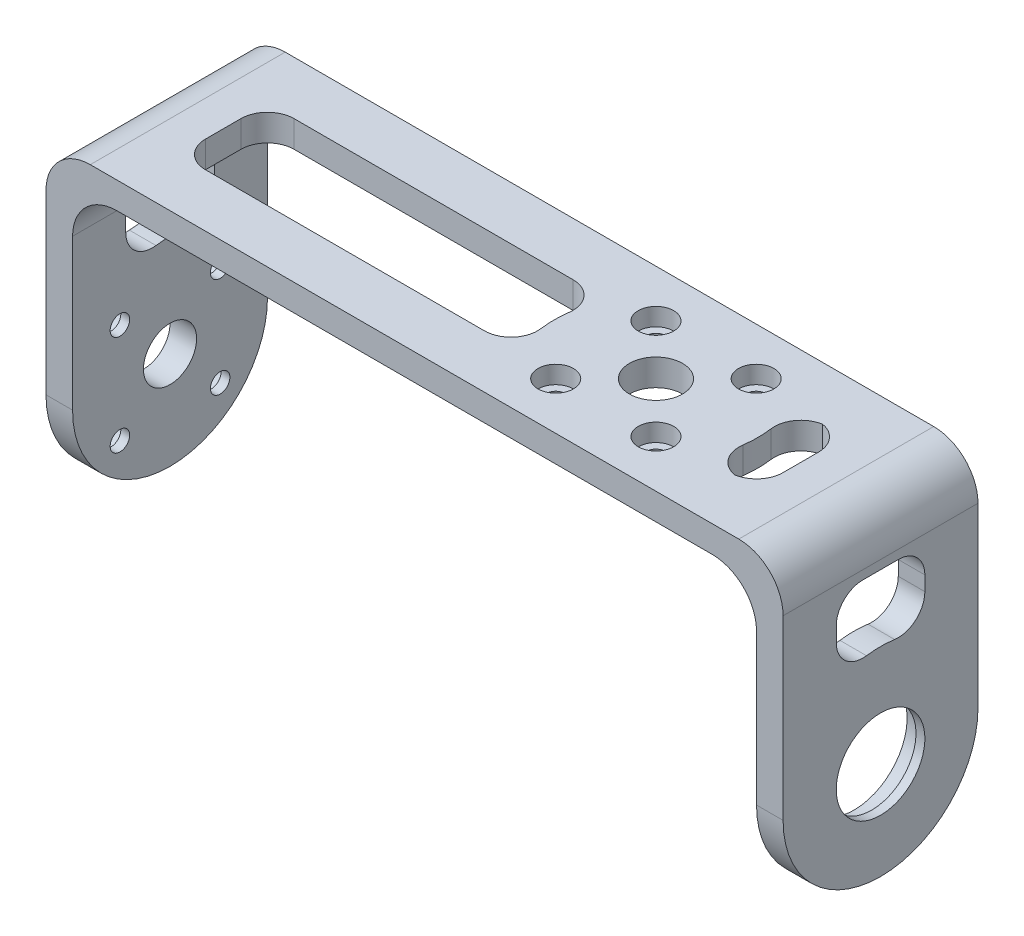
SolidWorks part; units mm, degrees
ref_plane "Front Plane" through (0, 0, 0) normal (0, 0, 1) x (1, 0, 0)
ref_plane "Top Plane" through (0, 0, 0) normal (0, 1, 0) x (1, 0, 0)
ref_plane "Right Plane" through (0, 0, 0) normal (1, 0, 0) x (0, 0, -1)
sketch "Sketch1" plane through (0, 0, 0) normal (0, 1, 0) x (1, 0, 0)
  line L0 (16.25, 0) -> (18.3713, 2.1213) construction
  line L1 (38.6, 11) -> (-38.6, 11)
  line L2 (38.6, 11) -> (38.6, -11)
  line L3 (38.6, -11) -> (-38.6, -11)
  line L4 (-38.6, 11) -> (-38.6, -11)
  line L5 (38.6, 11) -> (-38.6, -11) construction
  line L6 (38.6, -11) -> (-38.6, 11) construction
  line L7 (-38.6, 11) -> (-41.6, 11)
  line L8 (-38.6, 11) -> (-38.6, -11)
  line L9 (-38.6, -11) -> (-41.6, -11)
  line L10 (-41.6, 11) -> (-41.6, -11)
  line L11 (38.6, 11) -> (41.6, 11)
  line L12 (38.6, 11) -> (38.6, -11)
  line L13 (38.6, -11) -> (41.6, -11)
  line L14 (41.6, 11) -> (41.6, -11)
  line L15 (-32.6, 5) -> (-32.6, 11) construction
  line L16 (32.6, 5) -> (26.6062, 5)
  line L17 (32.6, 5) -> (32.6, -5)
  line L18 (32.6, -5) -> (26.6062, -5)
  line L19 (-32.6, 5) -> (-32.6, -5)
  line L20 (32.6, 5) -> (-32.6, -5) construction
  line L21 (32.6, -5) -> (-32.6, 5) construction
  line L22 (-32.6, 5) -> (-38.6, 5) construction
  line L23 (5.8938, 5) -> (-32.6, 5)
  line L24 (5.8938, -5) -> (-32.6, -5)
  circle A0 centre (16.25, 0) radius 3
  arc A1 (5.8938, 5) -> (5.8938, -5) centre (16.25, 0) ccw
  arc A2 (26.6062, -5) -> (26.6062, 5) centre (16.25, 0) ccw
  point P0 (0, 0)
  point P13 (0, 0)
  dimension "D5" = 6
  dimension "D8" = 23
  dimension "D1" = 77.2
  dimension "D2" = 22
  dimension "D3" = 3
  dimension "D4" = 22.35
  dimension "D6" = 45
  dimension "D7" = 6
extrude "Boss-Extrude1" add sketch "Sketch1" against normal blind 3 contours L1 L4 L3 L2 region at (37.7973, 0, 0)
extrude "Boss-Extrude2" add sketch "Sketch1<3>" against normal blind 36 separate body contours L7 L10 L9 L4 | L14 L11 L2 L13 region at (40.1, 0, 0) region at (-40.1, 0, 0)
sketch "Sketch1<3>" plane through (0, 0, 0) normal (0, 1, 0) x (1, 0, 0) same geometry as "Sketch1"
sketch "Sketch2" plane through (-41.6, 0, 0) normal (-1, 0, 0) x (0, 0, 1)
  line L0 (0, -25) -> (5.6569, -19.3431) construction
  line L3 (-11, -36) -> (11, -36) construction
  circle A0 centre (0, -25) radius 3
  circle A1 centre (5.6569, -19.3431) radius 1.1
  dimension "D1" = 6
  dimension "D5" = 2.2
  dimension "D2" = 11
  dimension "D3" = 8
  dimension "D4" = 45
extrude "Cut-Extrude1" cut sketch "Sketch2" against normal up to surface (3 mm away) contours A0 | A1 region at (-41.6, -25, 0) up to face at (-38.6, -18, 0)
sketch "Sketch4" plane through (0, 0, 0) normal (0, 1, 0) x (1, 0, 0)
  line L0 (21.9069, 5.6569) -> (16.25, 0) construction
  line L1 (38.6, 11) -> (-38.6, 11) construction
  circle A0 centre (21.9069, 5.6569) radius 1.1
  dimension "D3" = 2.2
  dimension "D1" = 45
  dimension "D2" = 8
extrude "Cut-Extrude3" cut sketch "Sketch4" against normal up to surface (3 mm away) up to face at (16.25, -3, 3)
pattern_circular "CirPattern2" count 4 over 360 about axis through (16.25, 0, 0) along (0, 1, 0) of "Cut-Extrude3"
sketch "Sketch5" plane through (-41.6, 0, 0) normal (-1, 0, 0) x (0, 0, 1)
  line L0 (-11, -6) -> (-5, -6) construction
  line L2 (-5, -14.6438) -> (-5, -6)
  line L3 (-5, -6) -> (5, -6)
  line L4 (5, -14.6438) -> (5, -6)
  line L5 (-11, -36) -> (-11, 0) construction
  line L6 (-5, -6) -> (-5, 0) construction
  line L7 (55, 0) -> (-55, 0) construction
  line L8 (5, -6) -> (11, -6) construction
  line L9 (11, -36) -> (11, 0) construction
  arc A0 (5, -14.6438) -> (-5, -14.6438) centre (0, -25) ccw
  circle A1 centre (0, -25) radius 3 construction
  point P1 (0, -17.3769)
  dimension "D2" = 23
  dimension "D1" = 6
extrude "Cut-Extrude4" cut sketch "Sketch5" against normal up to surface (83.2 mm away) up to face at (41.6, -18, 0)
sketch "Sketch6" plane through (38.6, 0, 0) normal (-1, 0, 0) x (0, 0, 1)
  circle A0 centre (0, -25) radius 6
  circle A1 centre (0, -25) radius 3 construction
  circle A2 centre (0, -25) radius 5
  dimension "D1" = 12
  dimension "D2" = 10
extrude "Cut-Extrude5" cut sketch "Sketch6" against normal offset from surface (2 mm away) 1 contours A2 | A0 A2 region at (38.6, -25, -5.8303) region at (38.6, -25, 0) up to face at (41.6, -10.036, 0)
extrude "Cut-Extrude6" cut sketch "Sketch6<3>" against normal up to surface (3 mm away) contours A2 region at (38.6, -25, 0) up to face at (41.6, -10.036, 0)
sketch "Sketch6<3>" plane through (38.6, 0, 0) normal (-1, 0, 0) x (0, 0, 1) same geometry as "Sketch6"
combine bodies "Combine1" operation type add bodies to combine 110 108 112
fillet "Fillet2" radius 5 4 edges at (41.6, 0, 0) (-41.6, 0, 0) (38.6, -3, 0) (-38.6, -3, 0)
pattern_circular "CirPattern3" count 4 over 360 about axis through (-30.1147, -25, 0) along (-1, 0, 0) of "Cut-Extrude1" reverse direction yes
fillet "Fillet3" radius 11 4 edges at (40.1, -36, 11) (40.1, -36, -11) (-40.1, -36, -11) (-40.1, -36, 11)
fillet "Fillet4" radius 3 16 edges at (40.1, -14.6438, -5) (40.1, -14.6438, 5) (39.8913, -6, 5) (39.8913, -6, -5) (32.6, -1.5, 5) (26.6062, -1.5, 5) (26.6062, -1.5, -5) (32.6, -1.5, -5) (5.8938, -1.5, 5) (-32.6, -1.5, 5) (-32.6, -1.5, -5) (5.8938, -1.5, -5) (-39.8913, -6, -5) (-39.8913, -6, 5) (-40.1, -14.6438, 5) (-40.1, -14.6438, -5)
sketch "Sketch8" plane through (0, 0, 0) normal (0, 1, 0) x (1, 0, 0)
  circle A0 centre (21.9069, -5.6569) radius 2
  dimension "D1" = 4
extrude "Cut-Extrude7" cut sketch "Sketch8" against normal offset from surface (2 mm away) 1 up to face at (10.5931, -3, -4.5569)
pattern_circular "CirPattern4" count 4 over 360 about axis through (16.25, 0, 0) along (0, 1, 0) of "Cut-Extrude7"
sketch "Sketch9" plane through (-41.6, 0, 0) normal (-1, 0, 0) x (0, 0, 1)
  circle A0 centre (5.6569, -19.3431) radius 2
  dimension "D1" = 4
extrude "Cut-Extrude8" cut sketch "Sketch9" against normal offset from surface (2 mm away) 1 up to face at (-38.6, -19.3431, -4.5569)
pattern_circular "CirPattern5" count 4 over 360 about axis through (-30.1147, -25, 0) along (-1, 0, 0) of "Cut-Extrude8"
